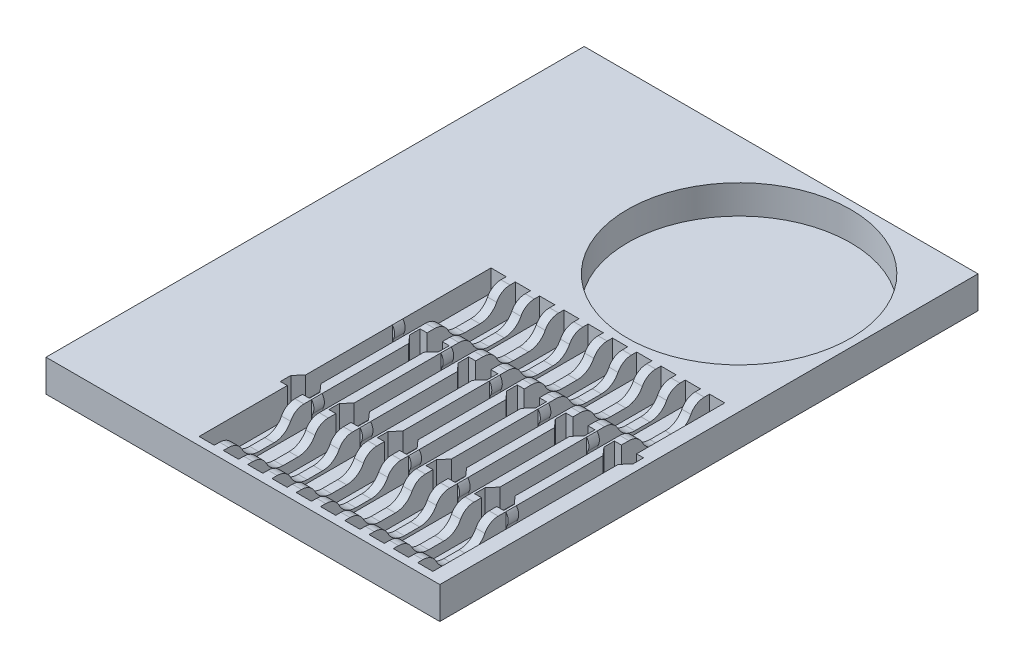
SolidWorks part; units mm, degrees
ref_plane "Front Plane" through (0, 0, 0) normal (0, 0, 1) x (1, 0, 0)
ref_plane "Top Plane" through (0, 0, 0) normal (0, 1, 0) x (1, 0, 0)
ref_plane "Right Plane" through (0, 0, 0) normal (1, 0, 0) x (0, 0, -1)
sketch "Sketch1" plane through (0, 0, 0) normal (0, 1, 0) x (1, 0, 0)
  line L0 (69.35, -28.9) -> (72, -25.9)
  line L37 (63.55, 11.7) -> (69.35, 11.7)
  line L38 (63.55, 11.7) -> (63.55, -21.9)
  line L39 (63.55, -21.9) -> (69.35, -21.9)
  line L40 (69.35, 11.7) -> (69.35, -21.9)
  line L41 (63.55, 11.7) -> (69.35, -21.9) construction
  line L42 (63.55, -21.9) -> (69.35, 11.7) construction
  line L43 (60.9, -21.9) -> (72, -21.9)
  line L44 (60.9, -21.9) -> (60.9, -25.9)
  line L45 (60.9, -25.9) -> (72, -25.9)
  line L46 (72, -21.9) -> (72, -25.9)
  line L47 (60.9, -21.9) -> (72, -25.9)
  line L48 (60.9, -25.9) -> (72, -21.9)
  line L49 (63.55, -28.9) -> (69.35, -28.9)
  line L50 (63.55, -28.9) -> (63.55, -99.5)
  line L51 (63.55, -99.5) -> (69.35, -99.5)
  line L52 (69.35, -28.9) -> (69.35, -99.5)
  line L53 (63.55, -28.9) -> (69.35, -99.5) construction
  line L54 (63.55, -99.5) -> (69.35, -28.9) construction
  line L55 (60.9, -25.9) -> (63.55, -28.9)
  line L56 (62.75, -61.9) -> (51.65, -65.9)
  line L57 (60.1, 11.7) -> (54.3, 11.7)
  line L58 (60.1, -65.9) -> (54.3, -65.9)
  line L59 (54.3, -99.5) -> (54.3, -65.9)
  line L60 (62.75, -65.9) -> (62.75, -61.9)
  line L61 (60.1, -99.5) -> (54.3, -65.9) construction
  line L62 (60.1, -58.9) -> (54.3, -58.9)
  line L63 (54.3, -58.9) -> (54.3, 11.7)
  line L64 (60.1, 11.7) -> (54.3, -58.9) construction
  line L65 (62.75, -61.9) -> (60.1, -58.9)
  line L66 (54.3, -58.9) -> (51.65, -61.9)
  line L67 (62.75, -65.9) -> (51.65, -61.9)
  line L68 (60.1, -99.5) -> (54.3, -99.5)
  line L69 (60.1, -99.5) -> (60.1, -65.9)
  line L70 (60.1, -65.9) -> (54.3, -99.5) construction
  line L71 (60.1, -58.9) -> (60.1, 11.7)
  line L72 (51.65, -65.9) -> (51.65, -61.9)
  line L73 (60.1, -58.9) -> (54.3, 11.7) construction
  line L74 (62.75, -65.9) -> (51.65, -65.9)
  line L75 (62.75, -61.9) -> (51.65, -61.9)
  line L76 (50.85, -28.9) -> (53.5, -25.9)
  line L77 (45.05, 11.7) -> (50.85, 11.7)
  line L78 (45.05, 11.7) -> (45.05, -21.9)
  line L79 (45.05, -21.9) -> (50.85, -21.9)
  line L80 (50.85, 11.7) -> (50.85, -21.9)
  line L81 (45.05, 11.7) -> (50.85, -21.9) construction
  line L82 (45.05, -21.9) -> (50.85, 11.7) construction
  line L83 (42.4, -21.9) -> (53.5, -21.9)
  line L84 (42.4, -21.9) -> (42.4, -25.9)
  line L85 (42.4, -25.9) -> (53.5, -25.9)
  line L86 (53.5, -21.9) -> (53.5, -25.9)
  line L87 (42.4, -21.9) -> (53.5, -25.9)
  line L88 (42.4, -25.9) -> (53.5, -21.9)
  line L89 (45.05, -28.9) -> (50.85, -28.9)
  line L90 (45.05, -28.9) -> (45.05, -99.5)
  line L91 (45.05, -99.5) -> (50.85, -99.5)
  line L92 (50.85, -28.9) -> (50.85, -99.5)
  line L93 (45.05, -28.9) -> (50.85, -99.5) construction
  line L94 (45.05, -99.5) -> (50.85, -28.9) construction
  line L95 (42.4, -25.9) -> (45.05, -28.9)
  line L96 (44.25, -61.9) -> (33.15, -65.9)
  line L97 (41.6, 11.7) -> (35.8, 11.7)
  line L98 (41.6, -65.9) -> (35.8, -65.9)
  line L99 (35.8, -99.5) -> (35.8, -65.9)
  line L100 (44.25, -65.9) -> (44.25, -61.9)
  line L101 (41.6, -99.5) -> (35.8, -65.9) construction
  line L102 (41.6, -58.9) -> (35.8, -58.9)
  line L103 (35.8, -58.9) -> (35.8, 11.7)
  line L104 (41.6, 11.7) -> (35.8, -58.9) construction
  line L105 (44.25, -61.9) -> (41.6, -58.9)
  line L106 (35.8, -58.9) -> (33.15, -61.9)
  line L107 (44.25, -65.9) -> (33.15, -61.9)
  line L108 (41.6, -99.5) -> (35.8, -99.5)
  line L109 (41.6, -99.5) -> (41.6, -65.9)
  line L110 (41.6, -65.9) -> (35.8, -99.5) construction
  line L111 (41.6, -58.9) -> (41.6, 11.7)
  line L112 (33.15, -65.9) -> (33.15, -61.9)
  line L113 (41.6, -58.9) -> (35.8, 11.7) construction
  line L114 (44.25, -65.9) -> (33.15, -65.9)
  line L115 (44.25, -61.9) -> (33.15, -61.9)
  line L116 (32.35, -28.9) -> (35, -25.9)
  line L117 (26.55, 11.7) -> (32.35, 11.7)
  line L118 (26.55, 11.7) -> (26.55, -21.9)
  line L119 (26.55, -21.9) -> (32.35, -21.9)
  line L120 (32.35, 11.7) -> (32.35, -21.9)
  line L121 (26.55, 11.7) -> (32.35, -21.9) construction
  line L122 (26.55, -21.9) -> (32.35, 11.7) construction
  line L123 (23.9, -21.9) -> (35, -21.9)
  line L124 (23.9, -21.9) -> (23.9, -25.9)
  line L125 (23.9, -25.9) -> (35, -25.9)
  line L126 (35, -21.9) -> (35, -25.9)
  line L127 (23.9, -21.9) -> (35, -25.9)
  line L128 (23.9, -25.9) -> (35, -21.9)
  line L129 (26.55, -28.9) -> (32.35, -28.9)
  line L130 (26.55, -28.9) -> (26.55, -99.5)
  line L131 (26.55, -99.5) -> (32.35, -99.5)
  line L132 (32.35, -28.9) -> (32.35, -99.5)
  line L133 (26.55, -28.9) -> (32.35, -99.5) construction
  line L134 (26.55, -99.5) -> (32.35, -28.9) construction
  line L135 (23.9, -25.9) -> (26.55, -28.9)
  line L136 (25.75, -61.9) -> (14.65, -65.9)
  line L137 (23.1, 11.7) -> (17.3, 11.7)
  line L138 (23.1, -65.9) -> (17.3, -65.9)
  line L139 (17.3, -99.5) -> (17.3, -65.9)
  line L140 (25.75, -65.9) -> (25.75, -61.9)
  line L141 (23.1, -99.5) -> (17.3, -65.9) construction
  line L142 (23.1, -58.9) -> (17.3, -58.9)
  line L143 (17.3, -58.9) -> (17.3, 11.7)
  line L144 (23.1, 11.7) -> (17.3, -58.9) construction
  line L145 (25.75, -61.9) -> (23.1, -58.9)
  line L146 (17.3, -58.9) -> (14.65, -61.9)
  line L147 (25.75, -65.9) -> (14.65, -61.9)
  line L148 (23.1, -99.5) -> (17.3, -99.5)
  line L149 (23.1, -99.5) -> (23.1, -65.9)
  line L150 (23.1, -65.9) -> (17.3, -99.5) construction
  line L151 (23.1, -58.9) -> (23.1, 11.7)
  line L152 (14.65, -65.9) -> (14.65, -61.9)
  line L153 (23.1, -58.9) -> (17.3, 11.7) construction
  line L154 (25.75, -65.9) -> (14.65, -65.9)
  line L155 (25.75, -61.9) -> (14.65, -61.9)
  line L156 (13.85, -28.9) -> (16.5, -25.9)
  line L157 (8.05, 11.7) -> (13.85, 11.7)
  line L158 (8.05, 11.7) -> (8.05, -21.9)
  line L159 (8.05, -21.9) -> (13.85, -21.9)
  line L160 (13.85, 11.7) -> (13.85, -21.9)
  line L161 (8.05, 11.7) -> (13.85, -21.9) construction
  line L162 (8.05, -21.9) -> (13.85, 11.7) construction
  line L163 (5.4, -21.9) -> (16.5, -21.9)
  line L164 (5.4, -21.9) -> (5.4, -25.9)
  line L165 (5.4, -25.9) -> (16.5, -25.9)
  line L166 (16.5, -21.9) -> (16.5, -25.9)
  line L167 (5.4, -21.9) -> (16.5, -25.9)
  line L168 (5.4, -25.9) -> (16.5, -21.9)
  line L169 (8.05, -28.9) -> (13.85, -28.9)
  line L170 (8.05, -28.9) -> (8.05, -99.5)
  line L171 (8.05, -99.5) -> (13.85, -99.5)
  line L172 (13.85, -28.9) -> (13.85, -99.5)
  line L173 (8.05, -28.9) -> (13.85, -99.5) construction
  line L174 (8.05, -99.5) -> (13.85, -28.9) construction
  line L175 (5.4, -25.9) -> (8.05, -28.9)
  line L176 (7.25, -61.9) -> (-3.85, -65.9)
  line L177 (4.6, 11.7) -> (-1.2, 11.7)
  line L178 (4.6, -65.9) -> (-1.2, -65.9)
  line L179 (-1.2, -99.5) -> (-1.2, -65.9)
  line L180 (7.25, -65.9) -> (7.25, -61.9)
  line L181 (4.6, -99.5) -> (-1.2, -65.9) construction
  line L182 (4.6, -58.9) -> (-1.2, -58.9)
  line L183 (-1.2, -58.9) -> (-1.2, 11.7)
  line L184 (4.6, 11.7) -> (-1.2, -58.9) construction
  line L185 (7.25, -61.9) -> (4.6, -58.9)
  line L186 (-1.2, -58.9) -> (-3.85, -61.9)
  line L187 (7.25, -65.9) -> (-3.85, -61.9)
  line L188 (4.6, -99.5) -> (-1.2, -99.5)
  line L189 (4.6, -99.5) -> (4.6, -65.9)
  line L190 (4.6, -65.9) -> (-1.2, -99.5) construction
  line L191 (4.6, -58.9) -> (4.6, 11.7)
  line L192 (-3.85, -65.9) -> (-3.85, -61.9)
  line L193 (4.6, -58.9) -> (-1.2, 11.7) construction
  line L194 (7.25, -65.9) -> (-3.85, -65.9)
  line L195 (7.25, -61.9) -> (-3.85, -61.9)
  line L196 (-4.65, -28.9) -> (-2, -25.9)
  line L197 (-10.45, 11.7) -> (-4.65, 11.7)
  line L198 (-10.45, 11.7) -> (-10.45, -21.9)
  line L199 (-10.45, -21.9) -> (-4.65, -21.9)
  line L200 (-4.65, 11.7) -> (-4.65, -21.9)
  line L201 (-10.45, 11.7) -> (-4.65, -21.9) construction
  line L202 (-10.45, -21.9) -> (-4.65, 11.7) construction
  line L203 (-13.1, -21.9) -> (-2, -21.9)
  line L204 (-13.1, -21.9) -> (-13.1, -25.9)
  line L205 (-13.1, -25.9) -> (-2, -25.9)
  line L206 (-2, -21.9) -> (-2, -25.9)
  line L207 (-13.1, -21.9) -> (-2, -25.9)
  line L208 (-13.1, -25.9) -> (-2, -21.9)
  line L209 (-10.45, -28.9) -> (-4.65, -28.9)
  line L210 (-10.45, -28.9) -> (-10.45, -99.5)
  line L211 (-10.45, -99.5) -> (-4.65, -99.5)
  line L212 (-4.65, -28.9) -> (-4.65, -99.5)
  line L213 (-10.45, -28.9) -> (-4.65, -99.5) construction
  line L214 (-10.45, -99.5) -> (-4.65, -28.9) construction
  line L215 (-13.1, -25.9) -> (-10.45, -28.9)
  line L216 (-11.25, -61.9) -> (-22.35, -65.9)
  line L217 (-13.9, 11.7) -> (-19.7, 11.7)
  line L218 (-13.9, -65.9) -> (-19.7, -65.9)
  line L219 (-19.7, -99.5) -> (-19.7, -65.9)
  line L220 (-11.25, -65.9) -> (-11.25, -61.9)
  line L221 (-13.9, -99.5) -> (-19.7, -65.9) construction
  line L222 (-13.9, -58.9) -> (-19.7, -58.9)
  line L223 (-19.7, -58.9) -> (-19.7, 11.7)
  line L224 (-13.9, 11.7) -> (-19.7, -58.9) construction
  line L225 (-11.25, -61.9) -> (-13.9, -58.9)
  line L226 (-19.7, -58.9) -> (-22.35, -61.9)
  line L227 (-11.25, -65.9) -> (-22.35, -61.9)
  line L228 (-13.9, -99.5) -> (-19.7, -99.5)
  line L229 (-13.9, -99.5) -> (-13.9, -65.9)
  line L230 (-13.9, -65.9) -> (-19.7, -99.5) construction
  line L231 (-13.9, -58.9) -> (-13.9, 11.7)
  line L232 (-22.35, -65.9) -> (-22.35, -61.9)
  line L233 (-13.9, -58.9) -> (-19.7, 11.7) construction
  line L234 (-11.25, -65.9) -> (-22.35, -65.9)
  line L235 (-11.25, -61.9) -> (-22.35, -61.9)
  line L237 (-55, 0) -> (55, 0) construction
  line L238 (-75, 102.5) -> (75, 102.5)
  line L239 (-75, 102.5) -> (-75, -102.5)
  line L240 (-75, -102.5) -> (75, -102.5)
  line L241 (75, 102.5) -> (75, -102.5)
  line L242 (-75, 102.5) -> (75, -102.5) construction
  line L243 (-75, -102.5) -> (75, 102.5) construction
  circle A0 centre (29.5, 57) radius 42.5
  point P11 (66.45, -23.9)
  point P35 (66.45, -5.1)
  point P41 (57.2, -63.9)
  point P42 (66.45, -64.2)
  point P50 (57.2, -82.7)
  point P56 (57.2, -23.6)
  point P62 (47.95, -23.9)
  point P66 (47.95, -5.1)
  point P72 (38.7, -63.9)
  point P74 (47.95, -64.2)
  point P82 (38.7, -82.7)
  point P88 (38.7, -23.6)
  point P93 (29.45, -23.9)
  point P97 (29.45, -5.1)
  point P103 (20.2, -63.9)
  point P104 (29.45, -64.2)
  point P112 (20.2, -82.7)
  point P118 (20.2, -23.6)
  point P123 (10.95, -23.9)
  point P127 (10.95, -5.1)
  point P133 (1.7, -63.9)
  point P134 (10.95, -64.2)
  point P142 (1.7, -82.7)
  point P148 (1.7, -23.6)
  point P153 (-7.55, -23.9)
  point P157 (-7.55, -5.1)
  point P163 (-16.8, -63.9)
  point P164 (-7.55, -64.2)
  point P172 (-16.8, -82.7)
  point P178 (-16.8, -23.6)
  point P195 (0, 0)
  dimension "D5" = 85
  dimension "D10" = 3
  dimension "D11" = 3
  dimension "D3" = 0.8
  dimension "D4" = 0.8
  dimension "D6" = 205
  dimension "D7" = 150
  dimension "D8" = 3
  dimension "D9" = 3
  dimension "D12" = 5.8
  dimension "D13" = 33.6
  dimension "D14" = 11.1
  dimension "D15" = 4
  dimension "D17" = 3
  dimension "D18" = 70.6
  dimension "D24" = 3
  dimension "D26" = 5
extrude "Boss-Extrude1" add sketch "Sketch1" along normal blind 1.2 contours L239 L240 L241 L238
extrude "Boss-Extrude2" add sketch "Sketch1<3>" along normal blind 11 from surface contours L241 L238 L239 L240 L215 L204 L203 L198 L197 L200 L206 L196 L212 L211 L210 L175 L164 L163 L158 L157 L160 L166 L156 L172 L171 L170 L135 L124 L123 L118 L117 L120 L126 L116 L132 L131 L130 L95 L84 L83 L78 L77 L80 region at (0, 0, -99.9598) starting at face at (0, 1.2, 0)
sketch "Sketch1<3>" plane through (0, 0, 0) normal (0, 1, 0) x (1, 0, 0) same geometry as "Sketch1"
extrude "Boss-Extrude3" add sketch "Sketch1<5>" along normal blind 2.7 from surface contours L222 L231 L217 L223 | L212 L209 L210 L211 | L182 L191 L177 L183 | L172 L169 L170 L171 | L142 L151 L137 L143 | L132 L129 L130 L131 | L102 L111 L97 L103 | L92 L89 L90 L91 | L62 L71 L57 L63 | L52 L49 L50 L51 region at (66.45, 0, 64.2) region at (57.2, 0, 23.6) region at (47.95, 0, 64.2) region at (38.7, 0, 23.6) region at (29.45, 0, 64.2) region at (20.2, 0, 23.6) region at (10.95, 0, 64.2) region at (1.7, 0, 23.6) region at (-7.55, 0, 64.2) region at (-16.8, 0, 23.6) starting at face at (-16.8, 1.2, 56.7333)
sketch "Sketch1<5>" plane through (0, 0, 0) normal (0, 1, 0) x (1, 0, 0) same geometry as "Sketch1"
sketch "Sketch2" plane through (75, 0, 0) normal (1, 0, 0) x (0, 0, -1)
  line L0 (-86.0419, 12.2) -> (-80.2419, 12.2) construction
  line L1 (-86.0419, 19.3) -> (-80.2419, 19.3)
  line L2 (-86.0419, 5.1) -> (-80.2419, 5.1)
  line L4 (102.5, 12.2) -> (-102.5, 12.2) construction
  line L5 (-28.9, 3.9) -> (-99.5, 3.9) construction
  line L6 (-102.5, 12.2) -> (-102.5, 0) construction
  arc A0 (-86.0419, 19.3) -> (-86.0419, 5.1) centre (-86.0419, 12.2) ccw
  arc A1 (-80.2419, 5.1) -> (-80.2419, 19.3) centre (-80.2419, 12.2) ccw
  arc A2 (-68.7839, 12.2) -> (-73.8841, 9.0396) centre (-68.7839, 6.5044) ccw
  arc A3 (-97.5, 12.2) -> (-92.3998, 9.0396) centre (-97.5, 6.5044) cw
  point P2 (-83.1419, 12.2)
  point P13 (0, 0)
  point P14 (0, 0)
  point P17 (0, 0)
  point P18 (0, 0)
  point P19 (-67.34, 10.5217)
  point P20 (-100.3057, 12.2)
  point P21 (-84.8747, 6.9981)
  point P22 (-74.4262, 10.4326)
  point P23 (0, 0)
  point P24 (-97.8834, 12.2)
  point P25 (-79.2214, 9.3652)
  point P26 (-81.8007, 18.3648)
  point P29 (-84.1306, 13.2251)
  point P30 (-83.6918, 12.2)
  point P31 (-83.5823, 12.2)
  point P32 (-97.3386, 12.2)
  point P33 (-80.0472, 19.3)
  line M4 (102.5, 12.2) -> (-102.5, 12.2)
  dimension "D1" = 20
  dimension "D2" = 1.2
  dimension "D3" = 6
  dimension "D4" = 5
extrude "Cut-Extrude1" cut sketch "Sketch2" against normal up to surface (94.7 mm away) from surface contours A3 A0 M4 | A2 A1 M4 | L2 A1 A0 region at (75, 9.0031, 83.1419) region at (75, 11.4909, 94.0647) region at (75, 11.4909, 72.2192) up to face at (-19.7, 6.7, 82.7) starting at face at (69.35, 8.05, 64.2)
ref_plane "Plane1" through (0, 0, 43.9) normal (0, 0, -1) x (-1, 0, 0)
mirror "Mirror1" about plane through (0, 0, 43.9) normal (0, 0, -1) of "Cut-Extrude1"
ref_plane "Plane2" through (0, 0, 65.9) normal (0, 0, 1) x (1, 0, 0)
sketch "Sketch4" plane through (0, 0, 65.9) normal (0, 0, 1) x (1, 0, 0)
  line L0 (63.55, 3.9) -> (69.35, 3.9) construction
  line L1 (69.35, 12.2) -> (69.35, 3.9)
  line L2 (69.35, 12.2) -> (69.35, 3.9) construction
  line L3 (-75, 12.2) -> (75, 12.2) construction
  line L4 (63.55, 3.9) -> (69.35, 3.9) construction
  line L5 (60.1, 12.2) -> (63.55, 12.2) construction
  line L6 (63.55, 5.1) -> (63.55, 9.0396) construction
  line L7 (69.35, 3.9) -> (63.55, 3.9)
  line L8 (63.55, 3.9) -> (63.55, 12.2)
  line L9 (45.05, 3.9) -> (45.05, 12.2)
  line L10 (50.85, 3.9) -> (45.05, 3.9)
  line L11 (50.85, 12.2) -> (50.85, 3.9)
  line L12 (26.55, 3.9) -> (26.55, 12.2)
  line L13 (32.35, 3.9) -> (26.55, 3.9)
  line L14 (32.35, 12.2) -> (32.35, 3.9)
  line L15 (8.05, 3.9) -> (8.05, 12.2)
  line L16 (13.85, 3.9) -> (8.05, 3.9)
  line L17 (13.85, 12.2) -> (13.85, 3.9)
  line L18 (-10.45, 3.9) -> (-10.45, 12.2)
  line L19 (-4.65, 3.9) -> (-10.45, 3.9)
  line L20 (-4.65, 12.2) -> (-4.65, 3.9)
  line L21 (-10.45, 5.1) -> (-10.45, 9.0396) construction
  circle A0 centre (66.45, 6.6) radius 2.7
  arc A1 (64.0257, 7.7887) -> (63.55, 12.2) centre (60.2954, 9.6177) ccw
  arc A2 (69.35, 12.2) -> (68.8743, 7.7887) centre (72.6046, 9.6177) ccw
  circle A3 centre (47.95, 6.6) radius 2.7
  arc A4 (45.5257, 7.7887) -> (45.05, 12.2) centre (41.7954, 9.6177) ccw
  arc A5 (50.85, 12.2) -> (50.3743, 7.7887) centre (54.1046, 9.6177) ccw
  circle A6 centre (29.45, 6.6) radius 2.7
  arc A7 (27.0257, 7.7887) -> (26.55, 12.2) centre (23.2954, 9.6177) ccw
  arc A8 (32.35, 12.2) -> (31.8743, 7.7887) centre (35.6046, 9.6177) ccw
  circle A9 centre (10.95, 6.6) radius 2.7
  arc A10 (8.5257, 7.7887) -> (8.05, 12.2) centre (4.7954, 9.6177) ccw
  arc A11 (13.85, 12.2) -> (13.3743, 7.7887) centre (17.1046, 9.6177) ccw
  circle A12 centre (-7.55, 6.6) radius 2.7
  arc A13 (-9.9743, 7.7887) -> (-10.45, 12.2) centre (-13.7046, 9.6177) ccw
  arc A14 (-4.65, 12.2) -> (-5.1257, 7.7887) centre (-1.3954, 9.6177) ccw
  point P10 (-9.4367, 3.9)
  point P22 (66.45, 3.9)
  point P23 (0, 0)
  dimension "D1" = 4
  dimension "D2" = 5.4
  dimension "D3" = 5
extrude "Boss-Extrude5" add sketch "Sketch4" against normal blind 4 contours A0 A1 L8 L7 | L1 A2 A0 L7 | A3 A4 L9 L10 | L11 A5 A3 L10 | A6 A7 L12 L13 | L14 A8 A6 L13 | A9 A10 L15 L16 | L17 A11 A9 L16 | A12 A13 L18 L19 | L20 A14 A12 L19 region at (69.2621, 8.05, 65.9) region at (65, 3.9879, 65.9) region at (45.1379, 8.05, 65.9) region at (49.9214, 4.6286, 65.9) region at (26.6379, 8.05, 65.9) region at (31.4214, 4.6286, 65.9) region at (8.1379, 8.05, 65.9) region at (12.9214, 4.6286, 65.9) region at (-10.3621, 8.05, 65.9) region at (-5.5786, 4.6286, 65.9)
ref_plane "Plane3" through (0, 0, 21.9) normal (0, 0, 1) x (1, 0, 0)
sketch "Sketch6" plane through (0, 0, 21.9) normal (0, 0, 1) x (1, 0, 0)
  line L0 (-13.9, 3.9) -> (-19.7, 3.9) construction
  line L1 (-13.9, 3.9) -> (-19.7, 3.9) construction
  line L2 (-13.9, 12.2) -> (-13.9, 9.0396) construction
  line L3 (-13.9, 12.2) -> (-10.45, 12.2) construction
  line L4 (-19.7, 12.2) -> (-19.7, 3.9) construction
  line L5 (-75, 12.2) -> (75, 12.2) construction
  line L6 (-19.7, 12.2) -> (-19.7, 3.9)
  line L7 (-19.7, 3.9) -> (-13.9, 3.9)
  line L8 (-13.9, 3.9) -> (-13.9, 12.2)
  line L9 (-1.2, 12.2) -> (-1.2, 3.9)
  line L10 (-1.2, 3.9) -> (4.6, 3.9)
  line L11 (4.6, 3.9) -> (4.6, 12.2)
  line L12 (17.3, 12.2) -> (17.3, 3.9)
  line L13 (17.3, 3.9) -> (23.1, 3.9)
  line L14 (23.1, 3.9) -> (23.1, 12.2)
  line L15 (35.8, 12.2) -> (35.8, 3.9)
  line L16 (35.8, 3.9) -> (41.6, 3.9)
  line L17 (41.6, 3.9) -> (41.6, 12.2)
  line L18 (54.3, 12.2) -> (54.3, 3.9)
  line L19 (54.3, 3.9) -> (60.1, 3.9)
  line L20 (60.1, 3.9) -> (60.1, 12.2)
  line L21 (60.1, 12.2) -> (60.1, 9.0396) construction
  circle A0 centre (-16.8, 6.6) radius 2.7
  arc A1 (-19.7, 12.2) -> (-19.2243, 7.7887) centre (-22.9546, 9.6177) cw
  arc A2 (-13.9, 12.2) -> (-14.3757, 7.7887) centre (-10.6454, 9.6177) ccw
  arc A3 (-1.2, 12.2) -> (-0.7243, 7.7887) centre (-4.4546, 9.6177) cw
  circle A4 centre (1.7, 6.6) radius 2.7
  arc A5 (4.6, 12.2) -> (4.1243, 7.7887) centre (7.8546, 9.6177) ccw
  arc A6 (17.3, 12.2) -> (17.7757, 7.7887) centre (14.0454, 9.6177) cw
  circle A7 centre (20.2, 6.6) radius 2.7
  arc A8 (23.1, 12.2) -> (22.6243, 7.7887) centre (26.3546, 9.6177) ccw
  arc A9 (35.8, 12.2) -> (36.2757, 7.7887) centre (32.5454, 9.6177) cw
  circle A10 centre (38.7, 6.6) radius 2.7
  arc A11 (41.6, 12.2) -> (41.1243, 7.7887) centre (44.8546, 9.6177) ccw
  arc A12 (54.3, 12.2) -> (54.7757, 7.7887) centre (51.0454, 9.6177) cw
  circle A13 centre (57.2, 6.6) radius 2.7
  arc A14 (60.1, 12.2) -> (59.6243, 7.7887) centre (63.3546, 9.6177) ccw
  point P2 (-16.8, 3.9)
  point P14 (0, 0)
  dimension "D1" = 5.4
  dimension "D2" = 4
  dimension "D3" = 5
extrude "Boss-Extrude6" add sketch "Sketch6" along normal blind 4 contours A1 L6 L7 A0 | L8 A2 A0 L7 | L11 A5 A4 L10 | A4 A3 L9 L10 | L14 A8 A7 L13 | A7 A6 L12 L13 | L17 A11 A10 L16 | A10 A9 L15 L16 | L20 A14 A13 L19 | A13 A12 L18 L19 region at (-18.9114, 10.0537, 21.9) region at (-14.8286, 4.6286, 21.9) region at (-0.4114, 10.0537, 21.9) region at (3.6714, 4.6286, 21.9) region at (18.0886, 10.0537, 21.9) region at (22.1714, 4.6286, 21.9) region at (36.5886, 10.0537, 21.9) region at (40.6714, 4.6286, 21.9) region at (55.0886, 10.0537, 21.9) region at (59.1714, 4.6286, 21.9)
ref_axis "Axis2" through (29.5, 12.2, -57) along (0, -1, 0)
ref_plane "Plane7" through (0, 0, -57) normal (0, 0, 1) x (1, 0, 0)
